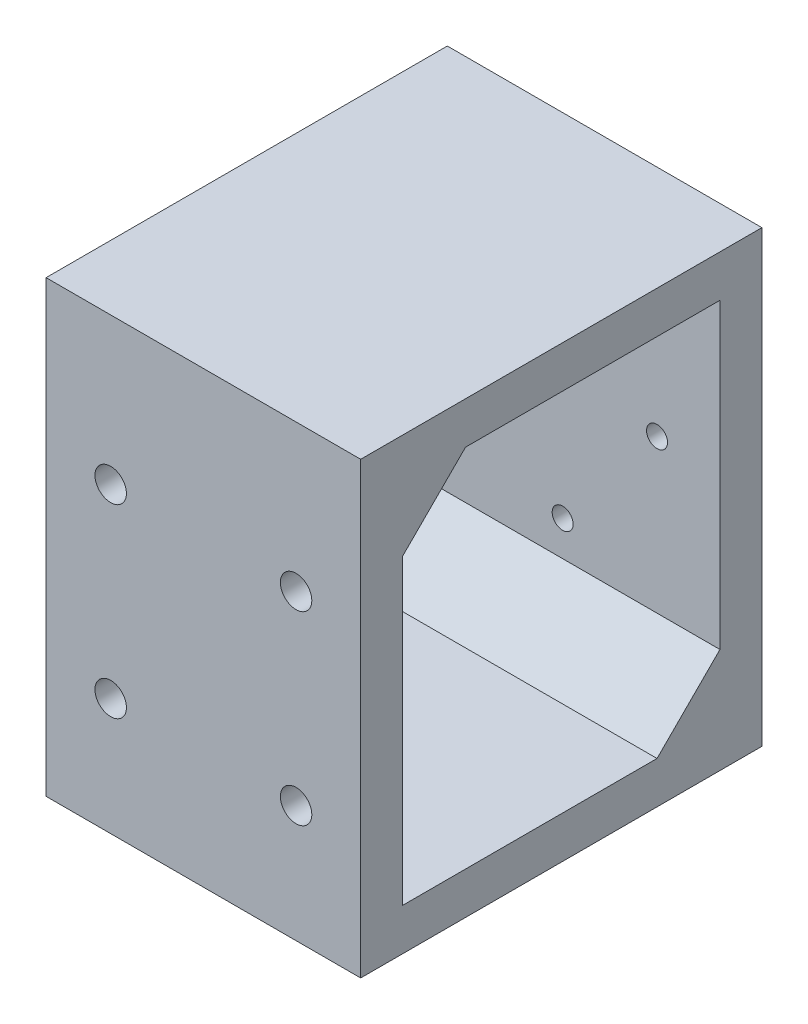
SolidWorks part; units mm, degrees
ref_plane "Front Plane" through (0, 0, 0) normal (0, 0, 1) x (1, 0, 0)
ref_plane "Top Plane" through (0, 0, 0) normal (0, 1, 0) x (1, 0, 0)
ref_plane "Right Plane" through (0, 0, 0) normal (1, 0, 0) x (0, 0, -1)
sketch "Sketch1" plane through (0, 0, 0) normal (1, 0, 0) x (0, 0, -1)
  line L1 (0, 0) -> (76.52, 0)
  line L2 (0, 0) -> (0, 85.68)
  line L3 (0, 85.68) -> (76.52, 85.68)
  line L4 (76.52, 0) -> (76.52, 85.68)
  line L5 (8, 77.68) -> (68.52, 77.68)
  line L6 (8, 77.68) -> (8, 8)
  line L7 (8, 8) -> (68.52, 8)
  line L8 (68.52, 77.68) -> (68.52, 8)
  dimension "D1" = 8
  dimension "D2" = 8
  dimension "D3" = 76.52
  dimension "D4" = 8
  dimension "D5" = 8
  dimension "D6" = 85.68
extrude "Boss-Extrude1" add sketch "Sketch1" along normal blind 30 and the other way blind 30
sketch "Sketch2" plane through (0, 0, -76.52) normal (0, 0, -1) x (-1, 0, 0)
  line L0 (0, 49.18) -> (0, 0) construction
  line L1 (-18, 49.18) -> (18, 49.18) construction
  line L2 (0, 71.68) -> (0, 26.68) construction
  line L3 (30, 85.68) -> (-30, 85.68) construction
  circle A0 centre (0, 71.68) radius 2
  circle A1 centre (18, 49.18) radius 2
  circle A3 centre (-18, 49.18) radius 2
  circle A4 centre (0, 26.68) radius 2
  point P6 (0, 49.18)
  point P9 (0, 49.18)
  dimension "D4" = 4
  dimension "D1" = 36.5
  dimension "D2" = 45
  dimension "D3" = 36
extrude "Cut-Extrude1" cut sketch "Sketch2" against normal blind 30
sketch "Sketch3" plane through (0, 0, 0) normal (0, 0, 1) x (1, 0, 0)
  line L0 (0, 0) -> (0, 40) construction
  line L1 (0, 40) -> (17.6777, 22.3223) construction
  circle A0 centre (0, 40) radius 25 construction
  circle A1 centre (17.6777, 22.3223) radius 3
  circle A2 centre (-17.6777, 22.3223) radius 3
  circle A3 centre (-17.6777, 57.6777) radius 3
  circle A4 centre (17.6777, 57.6777) radius 3
  circle A5 centre (17.6777, 57.6777) radius 5 construction
  point P15 (0, 40)
  dimension "D2" = 50
  dimension "D4" = 6
  dimension "D6" = 10
  dimension "D1" = 40
  dimension "D3" = 45
  dimension "D5" = 4
extrude "Cut-Extrude2" cut sketch "Sketch3" against normal blind 30
chamfer "Chamfer1" distance 12 angle 45 2 edges at (0, 8, -68.52) (0, 77.68, -8)
